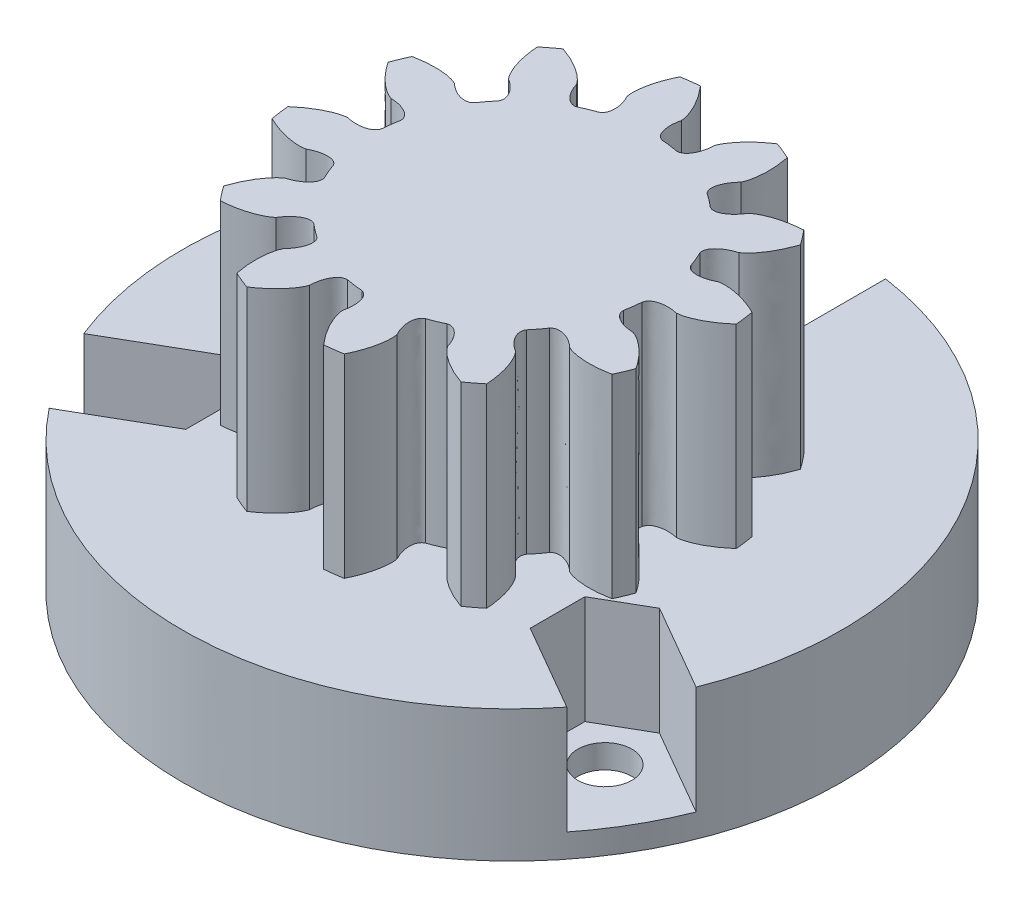
SolidWorks part; units mm, degrees
ref_plane "Front Plane" through (0, 0, 0) normal (0, 0, 1) x (1, 0, 0)
ref_plane "Top Plane" through (0, 0, 0) normal (0, 1, 0) x (1, 0, 0)
ref_plane "Right Plane" through (0, 0, 0) normal (1, 0, 0) x (0, 0, -1)
sketch "Sketch6" plane through (0, 0, 0) normal (0, 1, 0) x (1, 0, 0)
  circle A0 centre (0, 0) radius 19.5
  dimension "D1" = 39
extrude "Boss-Extrude1" add sketch "Sketch6" along normal blind 7.8 separate body
sketch "Sketch7" plane through (0, 7.8, 0) normal (0, 1, 0) x (1, 0, 0)
  circle A0 centre (0, 0) radius 10.5
  circle A1 centre (0, 0) radius 12.25
  circle A2 centre (0, 0) radius 8.3125
  dimension "D1" = 21
  dimension "D2" = 24.5
  dimension "D3" = 16.625
sketch "Sketch8" plane through (0, 0, 0) normal (0, 1, 0) x (1, 0, 0)
  line L0 (16.2938, 10.5) -> (-16.2938, 10.5) construction
  line L1 (-13.5138, 5.5814) -> (13.5138, 15.4186) construction
  line L2 (0, 0) -> (0, 15.4026) construction
  line L3 (0, 0) -> (-3.3746, 9.2717) construction
  line L4 (-3.3746, 9.2717) -> (0, 10.5)
  arc A0 (-3.3746, 9.2717) -> (0.1471, 9.8657) centre (0, 0) cw
  circle A1 centre (0, 0) radius 10.5 construction
  circle A2 centre (0, 0) radius 9.8668 construction
  point P3 (0, 10.5)
  point P9 (0, 10.5)
  dimension "D1" = 20
sketch "Sketch10" plane through (0, 0, 0) normal (0, 1, 0) x (1, 0, 0)
  line L0 (-3.3746, 9.2717) -> (0, 10.5)
  line L1 (-4.1825, 8.9364) -> (-0.1374, 10.8297) construction
  line L2 (-4.9575, 8.5309) -> (-0.3395, 11.2146) construction
  line L3 (-5.6936, 8.0583) -> (-0.6168, 11.6453) construction
  line L4 (-6.3849, 7.5224) -> (-0.9786, 12.1112) construction
  line L5 (-7.026, 6.9273) -> (-1.4331, 12.6) construction
  line L6 (-7.612, 6.2778) -> (-1.9866, 13.0986) construction
  line L7 (-1.6409, 9.7294) -> (0.1297, 10.028) construction
  arc A0 (-3.3746, 9.2717) -> (-4.1825, 8.9364) centre (0, 0) ccw
  circle A1 centre (0, 0) radius 9.8668 construction
  arc A2 (-4.1825, 8.9364) -> (-4.9575, 8.5309) centre (0, 0) ccw
  arc A3 (-4.9575, 8.5309) -> (-5.6936, 8.0583) centre (0, 0) ccw
  arc A4 (-5.6936, 8.0583) -> (-6.3849, 7.5224) centre (0, 0) ccw
  arc A5 (-6.3849, 7.5224) -> (-7.026, 6.9273) centre (0, 0) ccw
  arc A6 (-7.026, 6.9273) -> (-7.612, 6.2778) centre (0, 0) ccw
  arc A7 (-3.3746, 9.2717) -> (-1.6409, 9.7294) centre (0, 0) cw
  arc A8 (-1.6409, 9.7294) -> (0.1471, 9.8657) centre (0, 0) cw
  arc A9 (0.1471, 9.8657) -> (-3.3746, 9.2717) centre (0, 0) ccw construction
  dimension "D1" = 3.5912
  dimension "D3" = 4.4662
  dimension "D4" = 5.3412
  dimension "D5" = 6.2162
  dimension "D6" = 7.0912
  dimension "D7" = 7.9662
  dimension "D8" = 8.8412
  dimension "D10" = 1.7956
  dimension "D2" = 0.875
  dimension "D9" = 1.7956
sketch "Sketch15" plane through (0, 0, 0) normal (0, 1, 0) x (1, 0, 0)
  line L0 (-8.3796, 8.9356) -> (9.5703, 7.6467) construction
  line L1 (-3.3746, 9.2717) -> (0, 10.5) construction
  line L2 (-3.3746, 9.2717) -> (0, 10.5) construction
  line L3 (0.1471, 9.8657) -> (0.5954, 8.2912) construction
  line L4 (-6.7576, 10.2175) -> (10.7199, 5.9284) construction
  line L5 (0.1471, 9.8657) -> (0.2972, 8.4862) construction
  line L6 (-5.566, 10.9125) -> (11.3185, 4.6856) construction
  line L7 (0.1471, 9.8657) -> (0.1425, 8.8072) construction
  line L8 (-3.7093, 11.6749) -> (11.9317, 2.7744) construction
  line L9 (0.1471, 9.8657) -> (0.0874, 9.5144) construction
  line L10 (-4.577, 11.3628) -> (11.6892, 3.6641) construction
  line L11 (0.1471, 9.8657) -> (0.0811, 9.1582) construction
  line L12 (0.0874, 9.5144) -> (0.0811, 9.1582) construction
  line L13 (0.0811, 9.1582) -> (0.1425, 8.8072) construction
  line L14 (0.1425, 8.8072) -> (0.2972, 8.4862) construction
  line L15 (0.2972, 8.4862) -> (0.5954, 8.2912) construction
  circle A0 centre (0, 0) radius 12.25 construction
  arc A1 (-3.3746, 9.2717) -> (0.1471, 9.8657) centre (0, 0) cw construction
  circle A2 centre (0, 0) radius 8.3125 construction
  circle A3 centre (0, 0) radius 8.3125 construction
  dimension "D1" = 70
  dimension "D2" = 70
  dimension "D3" = 70
  dimension "D4" = 70
  dimension "D5" = 70
sketch "Sketch11" plane through (0, 7.8, 0) normal (0, 1, 0) x (1, 0, 0)
  line L1 (0, 0) -> (1.4144, 10.7435) construction
  line L2 (0, -9.8668) -> (0, -10.5) construction
  line L3 (0, -10.5) -> (0, -11.1332) construction
  line L5 (0, 0) -> (0, 11.9235) construction
  circle A1 centre (0, 0) radius 9.8668 construction
  circle A2 centre (0, 0) radius 10.5 construction
  arc A4 (0.5954, 8.2912) -> (1.5708, 8.1627) centre (0, 0) cw
  arc A5 (-1.9866, 13.0986) -> (5.3091, 12.1381) centre (0, 0) cw
  spline S0 degree 3 poles (-1.9866, 13.0986) (-1.6236, 12.7989) (-1.1413, 12.333) (-0.6251, 11.6711) (-0.3466, 11.2404) (-0.1429, 10.8555) (0.0426, 10.4112) (0.1353, 10.0836) (0.1471, 9.8657) knots 0 0 0 0 0.356747 0.505732 0.635125 0.744926 0.835134 1 1 1 1
  spline S1 degree 3 poles (2.4114, 9.5676) (2.4046, 9.3312) (2.3515, 8.9715) (2.1063, 8.43) (1.8374, 8.1563) (1.5708, 8.1627) knots 0 0 0 0 0.4 0.6 1 1 1 1
  spline S2 degree 3 poles (0.1471, 9.8657) (0.0924, 9.6356) (0.0506, 9.2744) (0.1474, 8.6879) (0.3362, 8.3539) (0.5954, 8.2912) knots 0 0 0 0 0.4 0.6 1 1 1 1
  spline S3 degree 3 poles (5.3091, 12.1381) (4.8809, 11.9426) (4.2944, 11.6174) (3.6245, 11.1117) (3.2441, 10.7677) (2.9477, 10.4486) (2.6535, 10.0675) (2.4791, 9.775) (2.4114, 9.5676) knots 0 0 0 0 0.356747 0.505732 0.635125 0.744926 0.835134 1 1 1 1
  dimension "D1" = 7.5
extrude "Boss-Extrude2" add sketch "Sketch7" along normal blind 11.5 contours A1
extrude "Cut-Extrude1" cut sketch "Sketch11" along normal up to surface (11.5 mm away) up to face at (0, 19.3, 12.25)
pattern_circular "CirPattern1" count 12 over 360 about axis through (0, 19.3, 0) along (0, -1, 0) of "Cut-Extrude1"
sketch "Sketch16" plane through (0, 7.8, 0) normal (0, 1, 0) x (1, 0, 0)
  line L6 (2.8, 16.6166) -> (2.8, 19.2979)
  line L7 (0, 18.2332) -> (-2.8, 16.6166) construction
  line L8 (-2.8, 16.6166) -> (-2.8, 13.3834)
  line L9 (-2.8, 13.3834) -> (0, 11.7668)
  line L10 (0, 11.7668) -> (2.8, 13.3834)
  line L11 (2.8, 13.3834) -> (2.8, 16.6166)
  line L12 (2.8, 16.6166) -> (0, 18.2332) construction
  line L13 (12.9904, -10.7332) -> (15.3125, -12.0738)
  line L14 (15.7904, -5.8834) -> (12.9904, -4.2668)
  line L15 (-2.8, 16.6166) -> (-2.8, 19.2979)
  line L16 (12.9904, -4.2668) -> (10.1904, -5.8834)
  line L17 (10.1904, -5.8834) -> (10.1904, -9.1166)
  line L18 (10.1904, -9.1166) -> (12.9904, -10.7332)
  line L19 (15.7904, -5.8834) -> (18.1125, -7.2241)
  line L20 (15.7904, -9.1166) -> (15.7904, -5.8834) construction
  line L21 (12.9904, -10.7332) -> (15.7904, -9.1166) construction
  line L22 (-15.7904, -5.8834) -> (-18.1125, -7.2241)
  line L23 (-12.9904, -10.7332) -> (-10.1904, -9.1166)
  line L24 (-10.1904, -9.1166) -> (-10.1904, -5.8834)
  line L25 (-10.1904, -5.8834) -> (-12.9904, -4.2668)
  line L26 (-12.9904, -4.2668) -> (-15.7904, -5.8834)
  line L27 (-12.9904, -10.7332) -> (-15.3125, -12.0738)
  line L28 (-15.7904, -9.1166) -> (-12.9904, -10.7332) construction
  line L29 (-15.7904, -5.8834) -> (-15.7904, -9.1166) construction
  circle A0 centre (0, 15) radius 1.6
  circle A2 centre (0, 0) radius 19.5 construction
  arc A3 (2.8, 19.2979) -> (-2.8, 19.2979) centre (0, 0) ccw
  circle A10 centre (0, 15) radius 2.8 construction
  circle A11 centre (12.9904, -7.5) radius 1.6
  arc A12 (15.3125, -12.0738) -> (18.1125, -7.2241) centre (0, 0) ccw
  circle A13 centre (12.9904, -7.5) radius 2.8 construction
  circle A14 centre (-12.9904, -7.5) radius 1.6
  arc A15 (-18.1125, -7.2241) -> (-15.3125, -12.0738) centre (0, 0) ccw
  circle A16 centre (-12.9904, -7.5) radius 2.8 construction
  point P24 (0, 0)
  point P39 (0, 0)
  dimension "D2" = 3.2
  dimension "D3" = 3
  dimension "D5" = 5.6
  dimension "D1" = 15
extrude "Cut-Extrude2" cut sketch "Sketch16" against normal blind 6.4
extrude "Cut-Extrude3" cut sketch "Sketch16<3>" against normal through all contours A0 | A14 | A11 region at (0, 7.8, -15) region at (12.9904, 7.8, 7.5) region at (-12.9904, 7.8, 7.5)
sketch "Sketch16<3>" plane through (0, 7.8, 0) normal (0, 1, 0) x (1, 0, 0) same geometry as "Sketch16"
equation "\"D1@Sketch7\"=\"Module@Drive Module.Assembly\"*\"Sun Teeth Num@Drive Module.Assembly\""
equation "\"D2@Sketch10\"=\"Module@Drive Module.Assembly\"*.5"
equation "\"D3@Sketch10\"=\"D1@Sketch10\"+\"D2@Sketch10\""
equation "\"D4@Sketch10\"=\"D3@Sketch10\"+\"D2@Sketch10\""
equation "\"D5@Sketch10\"=\"D4@Sketch10\"+\"D2@Sketch10\""
equation "\"D6@Sketch10\"=\"D5@Sketch10\"+\"D2@Sketch10\""
equation "\"D7@Sketch10\"=\"D6@Sketch10\"+\"D2@Sketch10\""
equation "\"D8@Sketch10\"=\"D7@Sketch10\"+\"D2@Sketch10\""
equation "\"D2@Sketch7\"=\"D1@Sketch7\"+2*\"Addendum@Drive Module.Assembly\""
equation "\"D3@Sketch7\"=\"D1@Sketch7\"-2*\"Dedendum@Drive Module.Assembly\""
equation "\"D1@Sketch15\"=90-\"Pressure Angle@Drive Module.Assembly\""
equation "\"D2@Sketch15\"=\"D1@Sketch15\""
equation "\"D3@Sketch15\"=\"D1@Sketch15\""
equation "\"D4@Sketch15\"=\"D1@Sketch15\""
equation "\"D5@Sketch15\"=\"D4@Sketch15\""
equation "\"D1@CirPattern1\"=\"Sun Teeth Num@Drive Module.Assembly\""
equation "\"D10@Sketch10\"=\"D1@Sketch10\"-\"D9@Sketch10\""
equation "\"D1@Sketch11\"=90/\"Sun Teeth Num@Drive Module.Assembly\""
equation "\"D1@Sketch6\"=  39"
equation "\"D1@Boss-Extrude2\"=\"Gear Thickness@Drive Module.Assembly\"-3.5"
